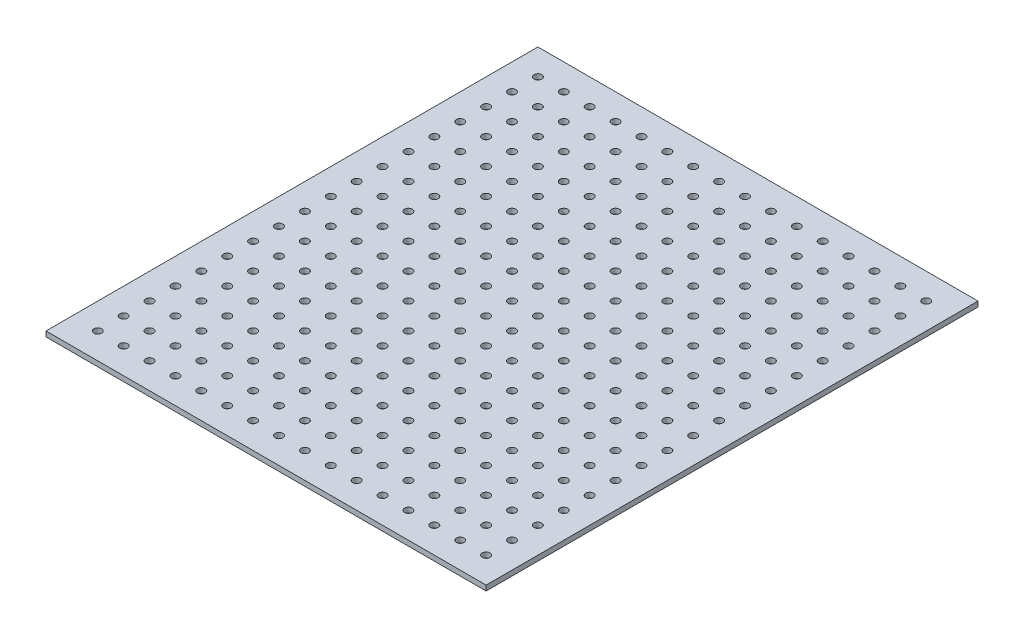
SolidWorks part; units mm, degrees
ref_plane "Front Plane" through (0, 0, 0) normal (0, 0, 1) x (1, 0, 0)
ref_plane "Top Plane" through (0, 0, 0) normal (0, 1, 0) x (1, 0, 0)
ref_plane "Right Plane" through (0, 0, 0) normal (1, 0, 0) x (0, 0, -1)
sketch "Sketch1" plane through (0, 0, 0) normal (0, 1, 0) x (1, 0, 0)
  line L1 (-85, 95) -> (85, 95)
  line L2 (-85, 95) -> (-85, -95)
  line L3 (-85, -95) -> (85, -95)
  line L4 (85, 95) -> (85, -95)
  line L5 (-85, 95) -> (85, -95) construction
  line L6 (-85, -95) -> (85, 95) construction
  point P0 (0, 0)
  dimension "D1" = 170
  dimension "D2" = 190
extrude "Boss-Extrude1" add sketch "Sketch1" along normal blind 2 contours L1 L4 L3 L2
sketch "Sketch2" plane through (0, 2, 0) normal (0, 1, 0) x (1, 0, 0)
  line L0 (-85, 95) -> (85, 95) construction
  line L1 (-85, 95) -> (-85, -95) construction
  line L3 (85, 95) -> (85, -95) construction
  line L4 (-85, -95) -> (85, -95) construction
  circle A0 centre (-75, 85) radius 1.5
  circle A1 centre (-65, 85) radius 1.5
  circle A2 centre (-55, 85) radius 1.5
  circle A3 centre (-45, 85) radius 1.5
  circle A4 centre (-35, 85) radius 1.5
  circle A5 centre (-25, 85) radius 1.5
  circle A6 centre (-15, 85) radius 1.5
  circle A7 centre (-5, 85) radius 1.5
  circle A8 centre (5, 85) radius 1.5
  circle A9 centre (15, 85) radius 1.5
  circle A10 centre (25, 85) radius 1.5
  circle A11 centre (35, 85) radius 1.5
  circle A12 centre (45, 85) radius 1.5
  circle A13 centre (55, 85) radius 1.5
  circle A14 centre (65, 85) radius 1.5
  circle A15 centre (75, 85) radius 1.5
  circle A16 centre (-65, 75) radius 1.5
  circle A17 centre (-55, 75) radius 1.5
  circle A18 centre (-45, 75) radius 1.5
  circle A19 centre (-35, 75) radius 1.5
  circle A20 centre (-25, 75) radius 1.5
  circle A21 centre (-15, 75) radius 1.5
  circle A22 centre (-5, 75) radius 1.5
  circle A23 centre (5, 75) radius 1.5
  circle A24 centre (15, 75) radius 1.5
  circle A25 centre (25, 75) radius 1.5
  circle A26 centre (35, 75) radius 1.5
  circle A27 centre (45, 75) radius 1.5
  circle A28 centre (55, 75) radius 1.5
  circle A29 centre (65, 75) radius 1.5
  circle A30 centre (75, 75) radius 1.5
  circle A31 centre (-65, 65) radius 1.5
  circle A32 centre (-55, 65) radius 1.5
  circle A33 centre (-45, 65) radius 1.5
  circle A34 centre (-35, 65) radius 1.5
  circle A35 centre (-25, 65) radius 1.5
  circle A36 centre (-15, 65) radius 1.5
  circle A37 centre (-5, 65) radius 1.5
  circle A38 centre (5, 65) radius 1.5
  circle A39 centre (15, 65) radius 1.5
  circle A40 centre (25, 65) radius 1.5
  circle A41 centre (35, 65) radius 1.5
  circle A42 centre (45, 65) radius 1.5
  circle A43 centre (55, 65) radius 1.5
  circle A44 centre (65, 65) radius 1.5
  circle A45 centre (75, 65) radius 1.5
  circle A46 centre (-65, 55) radius 1.5
  circle A47 centre (-55, 55) radius 1.5
  circle A48 centre (-45, 55) radius 1.5
  circle A49 centre (-35, 55) radius 1.5
  circle A50 centre (-25, 55) radius 1.5
  circle A51 centre (-15, 55) radius 1.5
  circle A52 centre (-5, 55) radius 1.5
  circle A53 centre (5, 55) radius 1.5
  circle A54 centre (15, 55) radius 1.5
  circle A55 centre (25, 55) radius 1.5
  circle A56 centre (35, 55) radius 1.5
  circle A57 centre (45, 55) radius 1.5
  circle A58 centre (55, 55) radius 1.5
  circle A59 centre (65, 55) radius 1.5
  circle A60 centre (75, 55) radius 1.5
  circle A61 centre (-65, 45) radius 1.5
  circle A62 centre (-55, 45) radius 1.5
  circle A63 centre (-45, 45) radius 1.5
  circle A64 centre (-35, 45) radius 1.5
  circle A65 centre (-25, 45) radius 1.5
  circle A66 centre (-15, 45) radius 1.5
  circle A67 centre (-5, 45) radius 1.5
  circle A68 centre (5, 45) radius 1.5
  circle A69 centre (15, 45) radius 1.5
  circle A70 centre (25, 45) radius 1.5
  circle A71 centre (35, 45) radius 1.5
  circle A72 centre (45, 45) radius 1.5
  circle A73 centre (55, 45) radius 1.5
  circle A74 centre (65, 45) radius 1.5
  circle A75 centre (75, 45) radius 1.5
  circle A76 centre (-65, 35) radius 1.5
  circle A77 centre (-55, 35) radius 1.5
  circle A78 centre (-45, 35) radius 1.5
  circle A79 centre (-35, 35) radius 1.5
  circle A80 centre (-25, 35) radius 1.5
  circle A81 centre (-15, 35) radius 1.5
  circle A82 centre (-5, 35) radius 1.5
  circle A83 centre (5, 35) radius 1.5
  circle A84 centre (15, 35) radius 1.5
  circle A85 centre (25, 35) radius 1.5
  circle A86 centre (35, 35) radius 1.5
  circle A87 centre (45, 35) radius 1.5
  circle A88 centre (55, 35) radius 1.5
  circle A89 centre (65, 35) radius 1.5
  circle A90 centre (75, 35) radius 1.5
  circle A91 centre (-65, 25) radius 1.5
  circle A92 centre (-55, 25) radius 1.5
  circle A93 centre (-45, 25) radius 1.5
  circle A94 centre (-35, 25) radius 1.5
  circle A95 centre (-25, 25) radius 1.5
  circle A96 centre (-15, 25) radius 1.5
  circle A97 centre (-5, 25) radius 1.5
  circle A98 centre (5, 25) radius 1.5
  circle A99 centre (15, 25) radius 1.5
  circle A100 centre (25, 25) radius 1.5
  circle A101 centre (35, 25) radius 1.5
  circle A102 centre (45, 25) radius 1.5
  circle A103 centre (55, 25) radius 1.5
  circle A104 centre (65, 25) radius 1.5
  circle A105 centre (75, 25) radius 1.5
  circle A106 centre (-65, 15) radius 1.5
  circle A107 centre (-55, 15) radius 1.5
  circle A108 centre (-45, 15) radius 1.5
  circle A109 centre (-35, 15) radius 1.5
  circle A110 centre (-25, 15) radius 1.5
  circle A111 centre (-15, 15) radius 1.5
  circle A112 centre (-5, 15) radius 1.5
  circle A113 centre (5, 15) radius 1.5
  circle A114 centre (15, 15) radius 1.5
  circle A115 centre (25, 15) radius 1.5
  circle A116 centre (35, 15) radius 1.5
  circle A117 centre (45, 15) radius 1.5
  circle A118 centre (55, 15) radius 1.5
  circle A119 centre (65, 15) radius 1.5
  circle A120 centre (75, 15) radius 1.5
  circle A121 centre (-65, 5) radius 1.5
  circle A122 centre (-55, 5) radius 1.5
  circle A123 centre (-45, 5) radius 1.5
  circle A124 centre (-35, 5) radius 1.5
  circle A125 centre (-25, 5) radius 1.5
  circle A126 centre (-15, 5) radius 1.5
  circle A127 centre (-5, 5) radius 1.5
  circle A128 centre (5, 5) radius 1.5
  circle A129 centre (15, 5) radius 1.5
  circle A130 centre (25, 5) radius 1.5
  circle A131 centre (35, 5) radius 1.5
  circle A132 centre (45, 5) radius 1.5
  circle A133 centre (55, 5) radius 1.5
  circle A134 centre (65, 5) radius 1.5
  circle A135 centre (75, 5) radius 1.5
  circle A136 centre (-65, -5) radius 1.5
  circle A137 centre (-55, -5) radius 1.5
  circle A138 centre (-45, -5) radius 1.5
  circle A139 centre (-35, -5) radius 1.5
  circle A140 centre (-25, -5) radius 1.5
  circle A141 centre (-15, -5) radius 1.5
  circle A142 centre (-5, -5) radius 1.5
  circle A143 centre (5, -5) radius 1.5
  circle A144 centre (15, -5) radius 1.5
  circle A145 centre (25, -5) radius 1.5
  circle A146 centre (35, -5) radius 1.5
  circle A147 centre (45, -5) radius 1.5
  circle A148 centre (55, -5) radius 1.5
  circle A149 centre (65, -5) radius 1.5
  circle A150 centre (75, -5) radius 1.5
  circle A151 centre (-65, -15) radius 1.5
  circle A152 centre (-55, -15) radius 1.5
  circle A153 centre (-45, -15) radius 1.5
  circle A154 centre (-35, -15) radius 1.5
  circle A155 centre (-25, -15) radius 1.5
  circle A156 centre (-15, -15) radius 1.5
  circle A157 centre (-5, -15) radius 1.5
  circle A158 centre (5, -15) radius 1.5
  circle A159 centre (15, -15) radius 1.5
  circle A160 centre (25, -15) radius 1.5
  circle A161 centre (35, -15) radius 1.5
  circle A162 centre (45, -15) radius 1.5
  circle A163 centre (55, -15) radius 1.5
  circle A164 centre (65, -15) radius 1.5
  circle A165 centre (75, -15) radius 1.5
  circle A166 centre (-65, -25) radius 1.5
  circle A167 centre (-55, -25) radius 1.5
  circle A168 centre (-45, -25) radius 1.5
  circle A169 centre (-35, -25) radius 1.5
  circle A170 centre (-25, -25) radius 1.5
  circle A171 centre (-15, -25) radius 1.5
  circle A172 centre (-5, -25) radius 1.5
  circle A173 centre (5, -25) radius 1.5
  circle A174 centre (15, -25) radius 1.5
  circle A175 centre (25, -25) radius 1.5
  circle A176 centre (35, -25) radius 1.5
  circle A177 centre (45, -25) radius 1.5
  circle A178 centre (55, -25) radius 1.5
  circle A179 centre (65, -25) radius 1.5
  circle A180 centre (75, -25) radius 1.5
  circle A181 centre (-65, -35) radius 1.5
  circle A182 centre (-55, -35) radius 1.5
  circle A183 centre (-45, -35) radius 1.5
  circle A184 centre (-35, -35) radius 1.5
  circle A185 centre (-25, -35) radius 1.5
  circle A186 centre (-15, -35) radius 1.5
  circle A187 centre (-5, -35) radius 1.5
  circle A188 centre (5, -35) radius 1.5
  circle A189 centre (15, -35) radius 1.5
  circle A190 centre (25, -35) radius 1.5
  circle A191 centre (35, -35) radius 1.5
  circle A192 centre (45, -35) radius 1.5
  circle A193 centre (55, -35) radius 1.5
  circle A194 centre (65, -35) radius 1.5
  circle A195 centre (75, -35) radius 1.5
  circle A196 centre (-65, -45) radius 1.5
  circle A197 centre (-55, -45) radius 1.5
  circle A198 centre (-45, -45) radius 1.5
  circle A199 centre (-35, -45) radius 1.5
  circle A200 centre (-25, -45) radius 1.5
  circle A201 centre (-15, -45) radius 1.5
  circle A202 centre (-5, -45) radius 1.5
  circle A203 centre (5, -45) radius 1.5
  circle A204 centre (15, -45) radius 1.5
  circle A205 centre (25, -45) radius 1.5
  circle A206 centre (35, -45) radius 1.5
  circle A207 centre (45, -45) radius 1.5
  circle A208 centre (55, -45) radius 1.5
  circle A209 centre (65, -45) radius 1.5
  circle A210 centre (75, -45) radius 1.5
  circle A211 centre (-65, -55) radius 1.5
  circle A212 centre (-55, -55) radius 1.5
  circle A213 centre (-45, -55) radius 1.5
  circle A214 centre (-35, -55) radius 1.5
  circle A215 centre (-25, -55) radius 1.5
  circle A216 centre (-15, -55) radius 1.5
  circle A217 centre (-5, -55) radius 1.5
  circle A218 centre (5, -55) radius 1.5
  circle A219 centre (15, -55) radius 1.5
  circle A220 centre (25, -55) radius 1.5
  circle A221 centre (35, -55) radius 1.5
  circle A222 centre (45, -55) radius 1.5
  circle A223 centre (55, -55) radius 1.5
  circle A224 centre (65, -55) radius 1.5
  circle A225 centre (75, -55) radius 1.5
  circle A226 centre (-65, -65) radius 1.5
  circle A227 centre (-55, -65) radius 1.5
  circle A228 centre (-45, -65) radius 1.5
  circle A229 centre (-35, -65) radius 1.5
  circle A230 centre (-25, -65) radius 1.5
  circle A231 centre (-15, -65) radius 1.5
  circle A232 centre (-5, -65) radius 1.5
  circle A233 centre (5, -65) radius 1.5
  circle A234 centre (15, -65) radius 1.5
  circle A235 centre (25, -65) radius 1.5
  circle A236 centre (35, -65) radius 1.5
  circle A237 centre (45, -65) radius 1.5
  circle A238 centre (55, -65) radius 1.5
  circle A239 centre (65, -65) radius 1.5
  circle A240 centre (75, -65) radius 1.5
  circle A241 centre (-65, -75) radius 1.5
  circle A242 centre (-55, -75) radius 1.5
  circle A243 centre (-45, -75) radius 1.5
  circle A244 centre (-35, -75) radius 1.5
  circle A245 centre (-25, -75) radius 1.5
  circle A246 centre (-15, -75) radius 1.5
  circle A247 centre (-5, -75) radius 1.5
  circle A248 centre (5, -75) radius 1.5
  circle A249 centre (15, -75) radius 1.5
  circle A250 centre (25, -75) radius 1.5
  circle A251 centre (35, -75) radius 1.5
  circle A252 centre (45, -75) radius 1.5
  circle A253 centre (55, -75) radius 1.5
  circle A254 centre (65, -75) radius 1.5
  circle A255 centre (75, -75) radius 1.5
  circle A256 centre (-65, -85) radius 1.5
  circle A257 centre (-55, -85) radius 1.5
  circle A258 centre (-45, -85) radius 1.5
  circle A259 centre (-35, -85) radius 1.5
  circle A260 centre (-25, -85) radius 1.5
  circle A261 centre (-15, -85) radius 1.5
  circle A262 centre (-5, -85) radius 1.5
  circle A263 centre (5, -85) radius 1.5
  circle A264 centre (15, -85) radius 1.5
  circle A265 centre (25, -85) radius 1.5
  circle A266 centre (35, -85) radius 1.5
  circle A267 centre (45, -85) radius 1.5
  circle A268 centre (55, -85) radius 1.5
  circle A269 centre (65, -85) radius 1.5
  circle A270 centre (75, -85) radius 1.5
  circle A271 centre (-75, 75) radius 1.5
  circle A272 centre (-75, 65) radius 1.5
  circle A273 centre (-75, 55) radius 1.5
  circle A274 centre (-75, 45) radius 1.5
  circle A275 centre (-75, 35) radius 1.5
  circle A276 centre (-75, 25) radius 1.5
  circle A277 centre (-75, 15) radius 1.5
  circle A278 centre (-75, 5) radius 1.5
  circle A279 centre (-75, -5) radius 1.5
  circle A280 centre (-75, -15) radius 1.5
  circle A281 centre (-75, -25) radius 1.5
  circle A282 centre (-75, -35) radius 1.5
  circle A283 centre (-75, -45) radius 1.5
  circle A284 centre (-75, -55) radius 1.5
  circle A285 centre (-75, -65) radius 1.5
  circle A286 centre (-75, -75) radius 1.5
  circle A287 centre (-75, -85) radius 1.5
  dimension "D1" = 3
  dimension "D2" = 10
  dimension "D3" = 10
  dimension "D6" = 10
  dimension "D7" = 10
  dimension "D4" = 16
  dimension "D5" = 18
extrude "Cut-Extrude1" cut sketch "Sketch2" against normal through all
